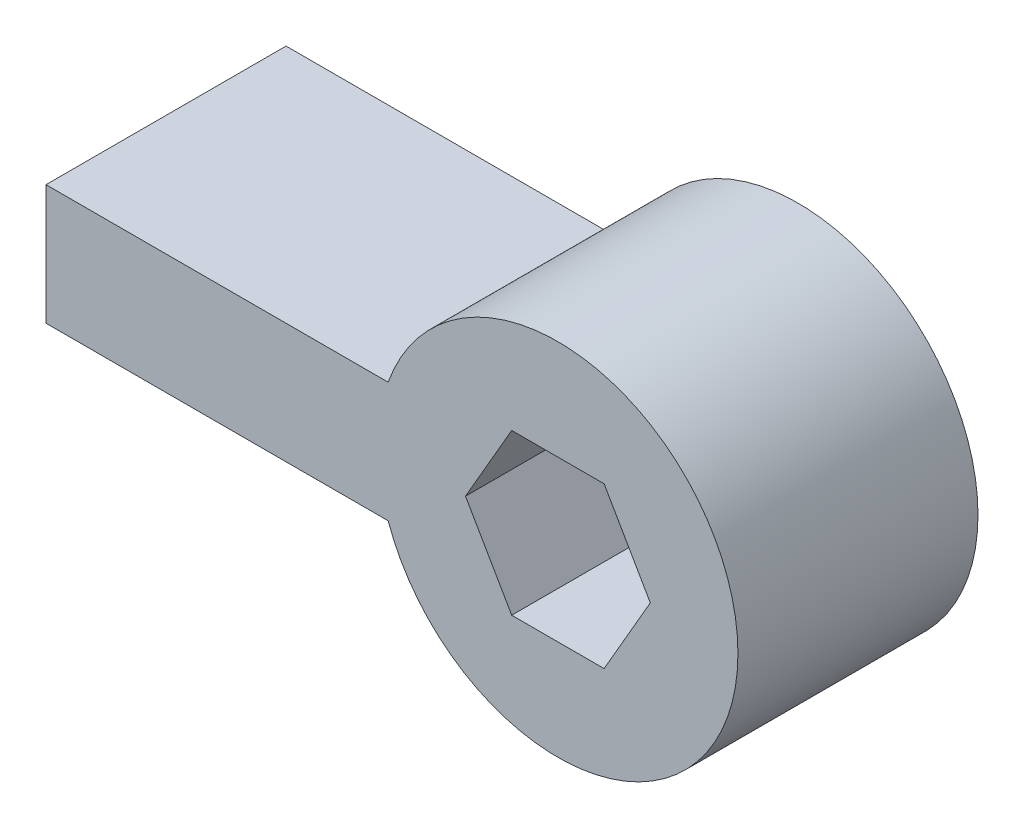
SolidWorks part; units mm, degrees
ref_plane "Front Plane" through (0, 0, 0) normal (0, 0, 1) x (1, 0, 0)
ref_plane "Top Plane" through (0, 0, 0) normal (0, 1, 0) x (1, 0, 0)
ref_plane "Right Plane" through (0, 0, 0) normal (1, 0, 0) x (0, 0, -1)
sketch "Sketch1" plane through (0, 0, 0) normal (0, 0, 1) x (1, 0, 0)
  line L0 (4.3947, 0) -> (6.7041, 0)
  line L1 (5.5494, 0) -> (5.5494, 2) construction
  line L3 (4.3947, 4) -> (3.24, 2)
  line L4 (6.7041, 4) -> (4.3947, 4)
  line L5 (7.8588, 2) -> (6.7041, 4)
  line L6 (6.7041, 0) -> (7.8588, 2)
  line L8 (3.24, 2) -> (4.3947, 0)
  line L9 (1.0426, 5.8059) -> (2.0853, 4) [skipped]
  circle A0 centre (5.5494, 2) radius 4.5
  point P17 (5.5494, 2)
  dimension "D2" = 4
  dimension "D5" = 9
  dimension "D1" = 6
  dimension "D3" = 4
  dimension "D4" = 4
extrude "Boss-Extrude1" add sketch "Sketch1" along normal blind 6
ref_plane "Plane1" through (0, 2, 0) normal (0, 1, 0) x (1, 0, 0)
sketch "Sketch2" plane through (0, 2, 0) normal (0, 1, 0) x (1, 0, 0)
  line L0 (3.24, 0) -> (1.0494, 0)
  line L2 (1.0494, -6) -> (3.24, -6)
  line L3 (1.0494, -6) -> (10.0494, -6) construction
  line L4 (3.24, -6) -> (3.24, 0)
  line L6 (1.0494, 0) -> (-7.2453, 0)
  line L7 (-7.2453, -6) -> (1.0494, -6)
  line L8 (-7.2453, 0) -> (-7.2453, -6)
extrude "Boss-Extrude2" add sketch "Sketch2" along normal blind 1.5 and the other way blind 1.5
